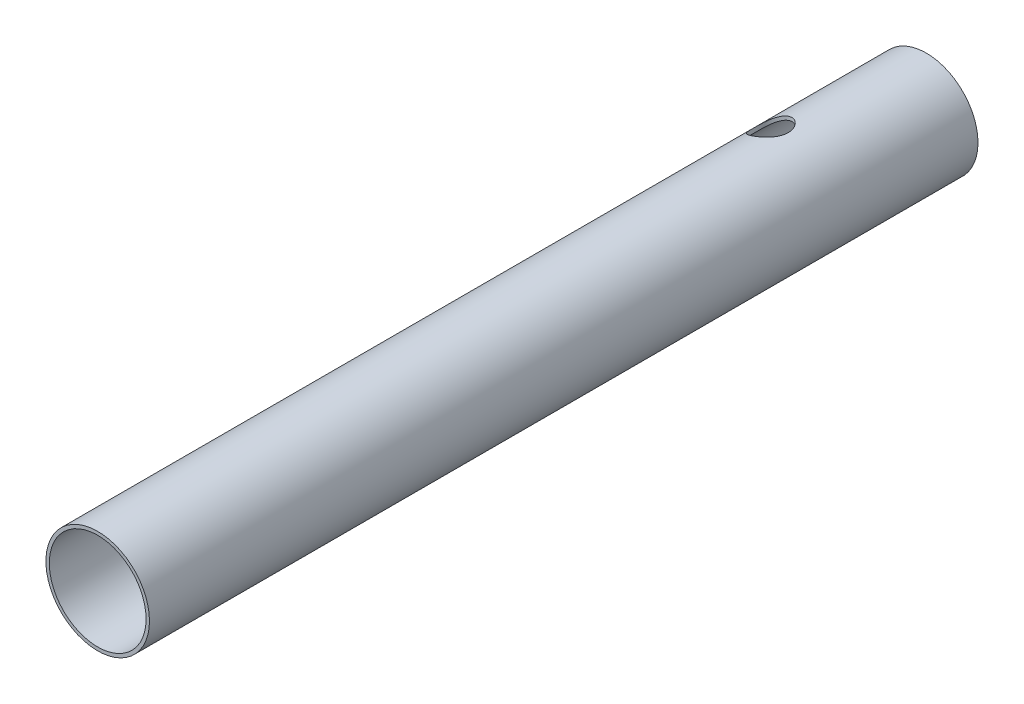
SolidWorks part; units mm, degrees
ref_plane "Front Plane" through (0, 0, 0) normal (0, 0, 1) x (1, 0, 0)
ref_plane "Top Plane" through (0, 0, 0) normal (0, 1, 0) x (1, 0, 0)
ref_plane "Right Plane" through (0, 0, 0) normal (1, 0, 0) x (0, 0, -1)
sketch "Sketch1" plane through (0, 0, 0) normal (0, 0, 1) x (1, 0, 0)
  circle A0 centre (0, 0) radius 19.05 construction
  circle A1 centre (0, 0) radius 17.8054 construction
  point P3 (-19.05, 0)
  point P4 (19.05, 0)
  point P6 (-17.8054, 0)
  point P7 (17.8054, 0)
  dimension "OD" = 38.1
  dimension "Wall" = 1.2446
  dimension "ID" = 35.6108
sketch "Sketch2" plane through (0, 0, 0) normal (1, 0, 0) x (0, 0, -1)
  line L0 (152.4, 0) -> (-152.4, 0) construction
  line L2 (0, 19.05) -> (0, -19.05) construction
  line L3 (0, 19.05) -> (0, -19.05) construction
  line L4 (152.4, 19.05) -> (-152.4, 19.05) construction
  line L5 (152.4, -19.05) -> (-152.4, -19.05) construction
  line L6 (-152.4, -19.05) -> (-152.4, 19.05) construction
  line L7 (152.4, -19.05) -> (152.4, 19.05) construction
  line L8 (-114.3, -19.05) -> (-114.3, 19.05) construction
  line L9 (114.3, -19.05) -> (114.3, 19.05) construction
  point P3 (0, 0)
  point P9 (0, 19.05)
  point P11 (0, -19.05)
  point P13 (-152.4, 0)
  point P14 (152.4, 19.05)
  point P15 (-152.4, -19.05)
  point P16 (-152.4, 19.05)
  point P17 (-152.4, 0)
  point P18 (152.4, -19.05)
  point P19 (152.4, 0)
  point P22 (-114.3, 0)
  point P25 (114.3, 0)
  point P26 (-114.3, -19.05)
  point P27 (-114.3, 19.05)
  point P28 (114.3, 19.05)
  point P29 (114.3, -19.05)
  dimension "Length" = 304.8
  dimension "D1" = 38.1
sketch "Sketch3" plane through (0, 0, 0) normal (0, 0, 1) x (1, 0, 0)
  circle A0 centre (0, 0) radius 19.05 construction
  circle A1 centre (0, 0) radius 17.8054 construction
  circle A2 centre (0, 0) radius 19.05
  circle A3 centre (0, 0) radius 17.8054
extrude "Boss-Extrude1" add sketch "Sketch3" along normal mid plane 304.8
ref_plane "Plane1" through (0, 25.4, 0) normal (0, 1, 0) x (1, 0, 0)
sketch "Sketch4" plane through (0, 25.4, 0) normal (0, 1, 0) x (1, 0, 0)
  line L0 (19.05, 152.4) -> (-19.05, 152.4) construction
  line L1 (19.05, -152.4) -> (19.05, 152.4) construction
  circle A0 centre (-6.35, 101.6) radius 6.35
  dimension "D1" = 12.7
  dimension "D2" = 50.8
  dimension "D3" = 25.4
extrude "Cut-Extrude1" cut sketch "Sketch4" against normal through all
equation "\"D1@Sketch2\"=\"OD@Sketch1\""
equation "\"D1@Boss-Extrude1\"=\"Length@Sketch2\""
